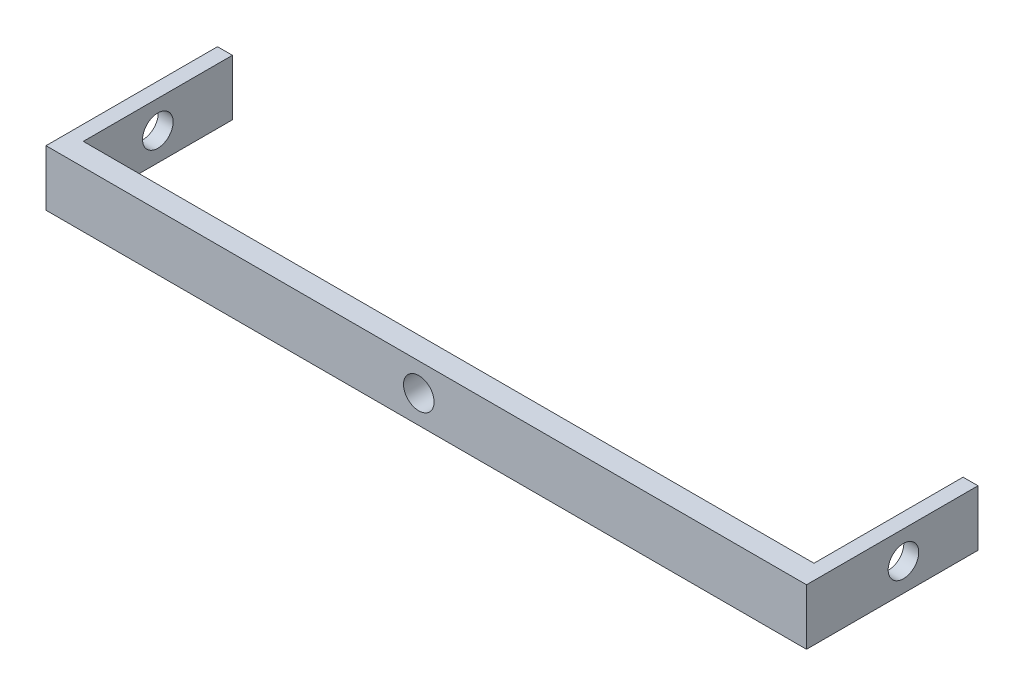
SolidWorks part; units mm, degrees
ref_plane "Front Plane" through (0, 0, 0) normal (0, 0, 1) x (1, 0, 0)
ref_plane "Top Plane" through (0, 0, 0) normal (0, 1, 0) x (1, 0, 0)
ref_plane "Right Plane" through (0, 0, 0) normal (1, 0, 0) x (0, 0, -1)
sketch "Sketch1" plane through (0, 0, 0) normal (0, 0, 1) x (1, 0, 0)
  line L0 (0, 0) -> (-16.4851, 0) construction
  line L1 (0, 0) -> (0, 8.651) construction
  line L3 (50, -3.75) -> (-50, -3.75)
  line L4 (50, -3.75) -> (50, 3.75)
  line L5 (50, 3.75) -> (-50, 3.75)
  line L6 (-50, -3.75) -> (-50, 3.75)
  line L7 (50, -3.75) -> (-50, 3.75) construction
  line L8 (50, 3.75) -> (-50, -3.75) construction
  point P4 (0, 0)
  dimension "D1" = 7.5
  dimension "D2" = 100
extrude "Boss-Extrude1" add sketch "Sketch1" along normal blind 3
sketch "Sketch2" plane through (0, 0, 0) normal (1, 0, 0) x (0, 0, -1)
  line L0 (-5, 3.75) -> (3.9833, 3.75) construction
  line L1 (-5, -3.75) -> (3.4696, -3.75) construction
  line L2 (0, 0) -> (-5.7048, 0) construction
  line L3 (0, 0) -> (0, -4.6795) construction
  line L5 (20, 3.9684) -> (20, -4.4628) construction
  line L6 (-3, 3.75) -> (-3, -3.75) construction
  line L7 (-3, 3.75) -> (20, 3.75)
  line L8 (20, 3.75) -> (20, -3.75)
  line L9 (20, -3.75) -> (-3, -3.75)
  line L10 (-3, -3.75) -> (-3, 3.75)
  dimension "D1" = 3.75
  dimension "D2" = 7.5
  dimension "D3" = 23
extrude "Boss-Extrude2" add sketch "Sketch2" along normal blind 2 from surface starting at face at (50, 0, 1.5)
extrude "Boss-Extrude3" add sketch "Sketch2<2>" along normal blind 2 from surface starting at face at (-50, 0, 1.5)
sketch "Sketch2<2>" plane through (0, 0, 0) normal (1, 0, 0) x (0, 0, -1) same geometry as "Sketch2"
sketch "Sketch3" plane through (0, 0, 0) normal (1, 0, 0) x (0, 0, -1)
  line L0 (20, 1.9295) -> (20, -6.8435) construction
  line L2 (0, 0) -> (0, -6.2775) construction
  line L3 (10, 4.0906) -> (10, -6.8735) construction
  line L4 (0, 0) -> (22.1388, 0) construction
  circle A0 centre (10, 0) radius 2.05
  dimension "D3" = 4.1
  dimension "D1" = 20
  dimension "D2" = 10
extrude "Cut-Extrude1" cut sketch "Sketch3" along normal through all from surface starting at face at (-50, 0, -8.5)
sketch "Sketch4" plane through (0, 0, 0) normal (0, 0, 1) x (1, 0, 0)
  line L0 (0, 0) -> (0, -8.2748) construction
  line L1 (0, 0) -> (-43.5369, 0) construction
  circle A0 centre (0, 0) radius 2.05
  dimension "D1" = 4.1
extrude "Cut-Extrude2" cut sketch "Sketch4" against normal through all from surface starting at face at (1, 0, 3)
